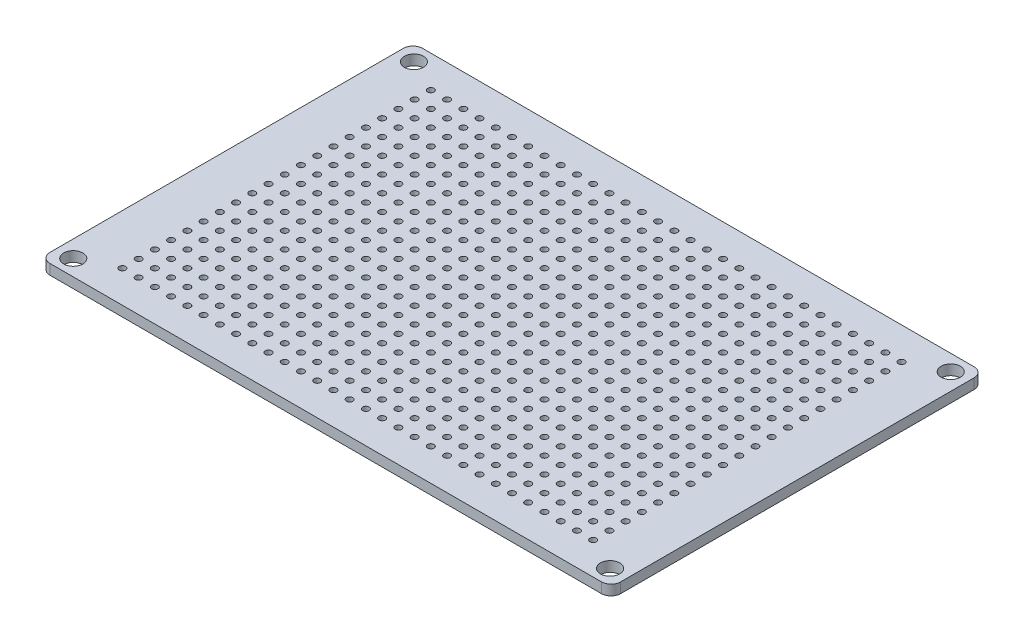
SolidWorks part; units mm, degrees
ref_plane "Front Plane" through (0, 0, 0) normal (0, 0, 1) x (1, 0, 0)
ref_plane "Top Plane" through (0, 0, 0) normal (0, 1, 0) x (1, 0, 0)
ref_plane "Right Plane" through (0, 0, 0) normal (1, 0, 0) x (0, 0, -1)
sketch "Sketch1" plane through (0, 0, 0) normal (0, 1, 0) x (1, 0, 0)
  line L0 (0, -29.15) -> (89.3, -29.15) construction
  line L1 (1.5, 0) -> (87.8, 0)
  line L2 (0, -1.5) -> (0, -56.8)
  line L3 (1.5, -58.3) -> (87.8, -58.3)
  line L4 (89.3, -1.5) -> (89.3, -56.8)
  line L5 (44.65, 0) -> (44.65, -58.3) construction
  line L6 (7.82, -5.02) -> (81.48, -5.02) construction
  line L7 (81.48, -5.02) -> (81.48, -53.28) construction
  line L9 (2.65, -2.5) -> (86.65, -2.5) construction
  line L10 (2.65, -2.5) -> (2.65, -55.8) construction
  line L11 (2.65, -55.8) -> (86.65, -55.8) construction
  line L12 (86.65, -2.5) -> (86.65, -55.8) construction
  circle A0 centre (7.82, -5.02) radius 0.5
  circle A1 centre (10.36, -5.02) radius 0.5
  circle A2 centre (12.9, -5.02) radius 0.5
  circle A3 centre (15.44, -5.02) radius 0.5
  circle A4 centre (17.98, -5.02) radius 0.5
  circle A5 centre (20.52, -5.02) radius 0.5
  circle A6 centre (23.06, -5.02) radius 0.5
  circle A7 centre (25.6, -5.02) radius 0.5
  circle A8 centre (28.14, -5.02) radius 0.5
  circle A9 centre (30.68, -5.02) radius 0.5
  circle A10 centre (33.22, -5.02) radius 0.5
  circle A11 centre (35.76, -5.02) radius 0.5
  circle A12 centre (38.3, -5.02) radius 0.5
  circle A13 centre (40.84, -5.02) radius 0.5
  circle A14 centre (43.38, -5.02) radius 0.5
  circle A15 centre (45.92, -5.02) radius 0.5
  circle A16 centre (48.46, -5.02) radius 0.5
  circle A17 centre (51, -5.02) radius 0.5
  circle A18 centre (53.54, -5.02) radius 0.5
  circle A19 centre (56.08, -5.02) radius 0.5
  circle A20 centre (58.62, -5.02) radius 0.5
  circle A21 centre (61.16, -5.02) radius 0.5
  circle A22 centre (63.7, -5.02) radius 0.5
  circle A23 centre (66.24, -5.02) radius 0.5
  circle A24 centre (68.78, -5.02) radius 0.5
  circle A25 centre (71.32, -5.02) radius 0.5
  circle A26 centre (73.86, -5.02) radius 0.5
  circle A27 centre (76.4, -5.02) radius 0.5
  circle A28 centre (78.94, -5.02) radius 0.5
  circle A29 centre (81.48, -5.02) radius 0.5
  circle A30 centre (10.36, -7.56) radius 0.5
  circle A31 centre (12.9, -7.56) radius 0.5
  circle A32 centre (15.44, -7.56) radius 0.5
  circle A33 centre (17.98, -7.56) radius 0.5
  circle A34 centre (20.52, -7.56) radius 0.5
  circle A35 centre (23.06, -7.56) radius 0.5
  circle A36 centre (25.6, -7.56) radius 0.5
  circle A37 centre (28.14, -7.56) radius 0.5
  circle A38 centre (30.68, -7.56) radius 0.5
  circle A39 centre (33.22, -7.56) radius 0.5
  circle A40 centre (35.76, -7.56) radius 0.5
  circle A41 centre (38.3, -7.56) radius 0.5
  circle A42 centre (40.84, -7.56) radius 0.5
  circle A43 centre (43.38, -7.56) radius 0.5
  circle A44 centre (45.92, -7.56) radius 0.5
  circle A45 centre (48.46, -7.56) radius 0.5
  circle A46 centre (51, -7.56) radius 0.5
  circle A47 centre (53.54, -7.56) radius 0.5
  circle A48 centre (56.08, -7.56) radius 0.5
  circle A49 centre (58.62, -7.56) radius 0.5
  circle A50 centre (61.16, -7.56) radius 0.5
  circle A51 centre (63.7, -7.56) radius 0.5
  circle A52 centre (66.24, -7.56) radius 0.5
  circle A53 centre (68.78, -7.56) radius 0.5
  circle A54 centre (71.32, -7.56) radius 0.5
  circle A55 centre (73.86, -7.56) radius 0.5
  circle A56 centre (76.4, -7.56) radius 0.5
  circle A57 centre (78.94, -7.56) radius 0.5
  circle A58 centre (81.48, -7.56) radius 0.5
  circle A59 centre (10.36, -10.1) radius 0.5
  circle A60 centre (12.9, -10.1) radius 0.5
  circle A61 centre (15.44, -10.1) radius 0.5
  circle A62 centre (17.98, -10.1) radius 0.5
  circle A63 centre (20.52, -10.1) radius 0.5
  circle A64 centre (23.06, -10.1) radius 0.5
  circle A65 centre (25.6, -10.1) radius 0.5
  circle A66 centre (28.14, -10.1) radius 0.5
  circle A67 centre (30.68, -10.1) radius 0.5
  circle A68 centre (33.22, -10.1) radius 0.5
  circle A69 centre (35.76, -10.1) radius 0.5
  circle A70 centre (38.3, -10.1) radius 0.5
  circle A71 centre (40.84, -10.1) radius 0.5
  circle A72 centre (43.38, -10.1) radius 0.5
  circle A73 centre (45.92, -10.1) radius 0.5
  circle A74 centre (48.46, -10.1) radius 0.5
  circle A75 centre (51, -10.1) radius 0.5
  circle A76 centre (53.54, -10.1) radius 0.5
  circle A77 centre (56.08, -10.1) radius 0.5
  circle A78 centre (58.62, -10.1) radius 0.5
  circle A79 centre (61.16, -10.1) radius 0.5
  circle A80 centre (63.7, -10.1) radius 0.5
  circle A81 centre (66.24, -10.1) radius 0.5
  circle A82 centre (68.78, -10.1) radius 0.5
  circle A83 centre (71.32, -10.1) radius 0.5
  circle A84 centre (73.86, -10.1) radius 0.5
  circle A85 centre (76.4, -10.1) radius 0.5
  circle A86 centre (78.94, -10.1) radius 0.5
  circle A87 centre (81.48, -10.1) radius 0.5
  circle A88 centre (10.36, -12.64) radius 0.5
  circle A89 centre (12.9, -12.64) radius 0.5
  circle A90 centre (15.44, -12.64) radius 0.5
  circle A91 centre (17.98, -12.64) radius 0.5
  circle A92 centre (20.52, -12.64) radius 0.5
  circle A93 centre (23.06, -12.64) radius 0.5
  circle A94 centre (25.6, -12.64) radius 0.5
  circle A95 centre (28.14, -12.64) radius 0.5
  circle A96 centre (30.68, -12.64) radius 0.5
  circle A97 centre (33.22, -12.64) radius 0.5
  circle A98 centre (35.76, -12.64) radius 0.5
  circle A99 centre (38.3, -12.64) radius 0.5
  circle A100 centre (40.84, -12.64) radius 0.5
  circle A101 centre (43.38, -12.64) radius 0.5
  circle A102 centre (45.92, -12.64) radius 0.5
  circle A103 centre (48.46, -12.64) radius 0.5
  circle A104 centre (51, -12.64) radius 0.5
  circle A105 centre (53.54, -12.64) radius 0.5
  circle A106 centre (56.08, -12.64) radius 0.5
  circle A107 centre (58.62, -12.64) radius 0.5
  circle A108 centre (61.16, -12.64) radius 0.5
  circle A109 centre (63.7, -12.64) radius 0.5
  circle A110 centre (66.24, -12.64) radius 0.5
  circle A111 centre (68.78, -12.64) radius 0.5
  circle A112 centre (71.32, -12.64) radius 0.5
  circle A113 centre (73.86, -12.64) radius 0.5
  circle A114 centre (76.4, -12.64) radius 0.5
  circle A115 centre (78.94, -12.64) radius 0.5
  circle A116 centre (81.48, -12.64) radius 0.5
  circle A117 centre (10.36, -15.18) radius 0.5
  circle A118 centre (12.9, -15.18) radius 0.5
  circle A119 centre (15.44, -15.18) radius 0.5
  circle A120 centre (17.98, -15.18) radius 0.5
  circle A121 centre (20.52, -15.18) radius 0.5
  circle A122 centre (23.06, -15.18) radius 0.5
  circle A123 centre (25.6, -15.18) radius 0.5
  circle A124 centre (28.14, -15.18) radius 0.5
  circle A125 centre (30.68, -15.18) radius 0.5
  circle A126 centre (33.22, -15.18) radius 0.5
  circle A127 centre (35.76, -15.18) radius 0.5
  circle A128 centre (38.3, -15.18) radius 0.5
  circle A129 centre (40.84, -15.18) radius 0.5
  circle A130 centre (43.38, -15.18) radius 0.5
  circle A131 centre (45.92, -15.18) radius 0.5
  circle A132 centre (48.46, -15.18) radius 0.5
  circle A133 centre (51, -15.18) radius 0.5
  circle A134 centre (53.54, -15.18) radius 0.5
  circle A135 centre (56.08, -15.18) radius 0.5
  circle A136 centre (58.62, -15.18) radius 0.5
  circle A137 centre (61.16, -15.18) radius 0.5
  circle A138 centre (63.7, -15.18) radius 0.5
  circle A139 centre (66.24, -15.18) radius 0.5
  circle A140 centre (68.78, -15.18) radius 0.5
  circle A141 centre (71.32, -15.18) radius 0.5
  circle A142 centre (73.86, -15.18) radius 0.5
  circle A143 centre (76.4, -15.18) radius 0.5
  circle A144 centre (78.94, -15.18) radius 0.5
  circle A145 centre (81.48, -15.18) radius 0.5
  circle A146 centre (10.36, -17.72) radius 0.5
  circle A147 centre (12.9, -17.72) radius 0.5
  circle A148 centre (15.44, -17.72) radius 0.5
  circle A149 centre (17.98, -17.72) radius 0.5
  circle A150 centre (20.52, -17.72) radius 0.5
  circle A151 centre (23.06, -17.72) radius 0.5
  circle A152 centre (25.6, -17.72) radius 0.5
  circle A153 centre (28.14, -17.72) radius 0.5
  circle A154 centre (30.68, -17.72) radius 0.5
  circle A155 centre (33.22, -17.72) radius 0.5
  circle A156 centre (35.76, -17.72) radius 0.5
  circle A157 centre (38.3, -17.72) radius 0.5
  circle A158 centre (40.84, -17.72) radius 0.5
  circle A159 centre (43.38, -17.72) radius 0.5
  circle A160 centre (45.92, -17.72) radius 0.5
  circle A161 centre (48.46, -17.72) radius 0.5
  circle A162 centre (51, -17.72) radius 0.5
  circle A163 centre (53.54, -17.72) radius 0.5
  circle A164 centre (56.08, -17.72) radius 0.5
  circle A165 centre (58.62, -17.72) radius 0.5
  circle A166 centre (61.16, -17.72) radius 0.5
  circle A167 centre (63.7, -17.72) radius 0.5
  circle A168 centre (66.24, -17.72) radius 0.5
  circle A169 centre (68.78, -17.72) radius 0.5
  circle A170 centre (71.32, -17.72) radius 0.5
  circle A171 centre (73.86, -17.72) radius 0.5
  circle A172 centre (76.4, -17.72) radius 0.5
  circle A173 centre (78.94, -17.72) radius 0.5
  circle A174 centre (81.48, -17.72) radius 0.5
  circle A175 centre (10.36, -20.26) radius 0.5
  circle A176 centre (12.9, -20.26) radius 0.5
  circle A177 centre (15.44, -20.26) radius 0.5
  circle A178 centre (17.98, -20.26) radius 0.5
  circle A179 centre (20.52, -20.26) radius 0.5
  circle A180 centre (23.06, -20.26) radius 0.5
  circle A181 centre (25.6, -20.26) radius 0.5
  circle A182 centre (28.14, -20.26) radius 0.5
  circle A183 centre (30.68, -20.26) radius 0.5
  circle A184 centre (33.22, -20.26) radius 0.5
  circle A185 centre (35.76, -20.26) radius 0.5
  circle A186 centre (38.3, -20.26) radius 0.5
  circle A187 centre (40.84, -20.26) radius 0.5
  circle A188 centre (43.38, -20.26) radius 0.5
  circle A189 centre (45.92, -20.26) radius 0.5
  circle A190 centre (48.46, -20.26) radius 0.5
  circle A191 centre (51, -20.26) radius 0.5
  circle A192 centre (53.54, -20.26) radius 0.5
  circle A193 centre (56.08, -20.26) radius 0.5
  circle A194 centre (58.62, -20.26) radius 0.5
  circle A195 centre (61.16, -20.26) radius 0.5
  circle A196 centre (63.7, -20.26) radius 0.5
  circle A197 centre (66.24, -20.26) radius 0.5
  circle A198 centre (68.78, -20.26) radius 0.5
  circle A199 centre (71.32, -20.26) radius 0.5
  circle A200 centre (73.86, -20.26) radius 0.5
  circle A201 centre (76.4, -20.26) radius 0.5
  circle A202 centre (78.94, -20.26) radius 0.5
  circle A203 centre (81.48, -20.26) radius 0.5
  circle A204 centre (10.36, -22.8) radius 0.5
  circle A205 centre (12.9, -22.8) radius 0.5
  circle A206 centre (15.44, -22.8) radius 0.5
  circle A207 centre (17.98, -22.8) radius 0.5
  circle A208 centre (20.52, -22.8) radius 0.5
  circle A209 centre (23.06, -22.8) radius 0.5
  circle A210 centre (25.6, -22.8) radius 0.5
  circle A211 centre (28.14, -22.8) radius 0.5
  circle A212 centre (30.68, -22.8) radius 0.5
  circle A213 centre (33.22, -22.8) radius 0.5
  circle A214 centre (35.76, -22.8) radius 0.5
  circle A215 centre (38.3, -22.8) radius 0.5
  circle A216 centre (40.84, -22.8) radius 0.5
  circle A217 centre (43.38, -22.8) radius 0.5
  circle A218 centre (45.92, -22.8) radius 0.5
  circle A219 centre (48.46, -22.8) radius 0.5
  circle A220 centre (51, -22.8) radius 0.5
  circle A221 centre (53.54, -22.8) radius 0.5
  circle A222 centre (56.08, -22.8) radius 0.5
  circle A223 centre (58.62, -22.8) radius 0.5
  circle A224 centre (61.16, -22.8) radius 0.5
  circle A225 centre (63.7, -22.8) radius 0.5
  circle A226 centre (66.24, -22.8) radius 0.5
  circle A227 centre (68.78, -22.8) radius 0.5
  circle A228 centre (71.32, -22.8) radius 0.5
  circle A229 centre (73.86, -22.8) radius 0.5
  circle A230 centre (76.4, -22.8) radius 0.5
  circle A231 centre (78.94, -22.8) radius 0.5
  circle A232 centre (81.48, -22.8) radius 0.5
  circle A233 centre (10.36, -25.34) radius 0.5
  circle A234 centre (12.9, -25.34) radius 0.5
  circle A235 centre (15.44, -25.34) radius 0.5
  circle A236 centre (17.98, -25.34) radius 0.5
  circle A237 centre (20.52, -25.34) radius 0.5
  circle A238 centre (23.06, -25.34) radius 0.5
  circle A239 centre (25.6, -25.34) radius 0.5
  circle A240 centre (28.14, -25.34) radius 0.5
  circle A241 centre (30.68, -25.34) radius 0.5
  circle A242 centre (33.22, -25.34) radius 0.5
  circle A243 centre (35.76, -25.34) radius 0.5
  circle A244 centre (38.3, -25.34) radius 0.5
  circle A245 centre (40.84, -25.34) radius 0.5
  circle A246 centre (43.38, -25.34) radius 0.5
  circle A247 centre (45.92, -25.34) radius 0.5
  circle A248 centre (48.46, -25.34) radius 0.5
  circle A249 centre (51, -25.34) radius 0.5
  circle A250 centre (53.54, -25.34) radius 0.5
  circle A251 centre (56.08, -25.34) radius 0.5
  circle A252 centre (58.62, -25.34) radius 0.5
  circle A253 centre (61.16, -25.34) radius 0.5
  circle A254 centre (63.7, -25.34) radius 0.5
  circle A255 centre (66.24, -25.34) radius 0.5
  circle A256 centre (68.78, -25.34) radius 0.5
  circle A257 centre (71.32, -25.34) radius 0.5
  circle A258 centre (73.86, -25.34) radius 0.5
  circle A259 centre (76.4, -25.34) radius 0.5
  circle A260 centre (78.94, -25.34) radius 0.5
  circle A261 centre (81.48, -25.34) radius 0.5
  circle A262 centre (10.36, -27.88) radius 0.5
  circle A263 centre (12.9, -27.88) radius 0.5
  circle A264 centre (15.44, -27.88) radius 0.5
  circle A265 centre (17.98, -27.88) radius 0.5
  circle A266 centre (20.52, -27.88) radius 0.5
  circle A267 centre (23.06, -27.88) radius 0.5
  circle A268 centre (25.6, -27.88) radius 0.5
  circle A269 centre (28.14, -27.88) radius 0.5
  circle A270 centre (30.68, -27.88) radius 0.5
  circle A271 centre (33.22, -27.88) radius 0.5
  circle A272 centre (35.76, -27.88) radius 0.5
  circle A273 centre (38.3, -27.88) radius 0.5
  circle A274 centre (40.84, -27.88) radius 0.5
  circle A275 centre (43.38, -27.88) radius 0.5
  circle A276 centre (45.92, -27.88) radius 0.5
  circle A277 centre (48.46, -27.88) radius 0.5
  circle A278 centre (51, -27.88) radius 0.5
  circle A279 centre (53.54, -27.88) radius 0.5
  circle A280 centre (56.08, -27.88) radius 0.5
  circle A281 centre (58.62, -27.88) radius 0.5
  circle A282 centre (61.16, -27.88) radius 0.5
  circle A283 centre (63.7, -27.88) radius 0.5
  circle A284 centre (66.24, -27.88) radius 0.5
  circle A285 centre (68.78, -27.88) radius 0.5
  circle A286 centre (71.32, -27.88) radius 0.5
  circle A287 centre (73.86, -27.88) radius 0.5
  circle A288 centre (76.4, -27.88) radius 0.5
  circle A289 centre (78.94, -27.88) radius 0.5
  circle A290 centre (81.48, -27.88) radius 0.5
  circle A291 centre (10.36, -30.42) radius 0.5
  circle A292 centre (12.9, -30.42) radius 0.5
  circle A293 centre (15.44, -30.42) radius 0.5
  circle A294 centre (17.98, -30.42) radius 0.5
  circle A295 centre (20.52, -30.42) radius 0.5
  circle A296 centre (23.06, -30.42) radius 0.5
  circle A297 centre (25.6, -30.42) radius 0.5
  circle A298 centre (28.14, -30.42) radius 0.5
  circle A299 centre (30.68, -30.42) radius 0.5
  circle A300 centre (33.22, -30.42) radius 0.5
  circle A301 centre (35.76, -30.42) radius 0.5
  circle A302 centre (38.3, -30.42) radius 0.5
  circle A303 centre (40.84, -30.42) radius 0.5
  circle A304 centre (43.38, -30.42) radius 0.5
  circle A305 centre (45.92, -30.42) radius 0.5
  circle A306 centre (48.46, -30.42) radius 0.5
  circle A307 centre (51, -30.42) radius 0.5
  circle A308 centre (53.54, -30.42) radius 0.5
  circle A309 centre (56.08, -30.42) radius 0.5
  circle A310 centre (58.62, -30.42) radius 0.5
  circle A311 centre (61.16, -30.42) radius 0.5
  circle A312 centre (63.7, -30.42) radius 0.5
  circle A313 centre (66.24, -30.42) radius 0.5
  circle A314 centre (68.78, -30.42) radius 0.5
  circle A315 centre (71.32, -30.42) radius 0.5
  circle A316 centre (73.86, -30.42) radius 0.5
  circle A317 centre (76.4, -30.42) radius 0.5
  circle A318 centre (78.94, -30.42) radius 0.5
  circle A319 centre (81.48, -30.42) radius 0.5
  circle A320 centre (10.36, -32.96) radius 0.5
  circle A321 centre (12.9, -32.96) radius 0.5
  circle A322 centre (15.44, -32.96) radius 0.5
  circle A323 centre (17.98, -32.96) radius 0.5
  circle A324 centre (20.52, -32.96) radius 0.5
  circle A325 centre (23.06, -32.96) radius 0.5
  circle A326 centre (25.6, -32.96) radius 0.5
  circle A327 centre (28.14, -32.96) radius 0.5
  circle A328 centre (30.68, -32.96) radius 0.5
  circle A329 centre (33.22, -32.96) radius 0.5
  circle A330 centre (35.76, -32.96) radius 0.5
  circle A331 centre (38.3, -32.96) radius 0.5
  circle A332 centre (40.84, -32.96) radius 0.5
  circle A333 centre (43.38, -32.96) radius 0.5
  circle A334 centre (45.92, -32.96) radius 0.5
  circle A335 centre (48.46, -32.96) radius 0.5
  circle A336 centre (51, -32.96) radius 0.5
  circle A337 centre (53.54, -32.96) radius 0.5
  circle A338 centre (56.08, -32.96) radius 0.5
  circle A339 centre (58.62, -32.96) radius 0.5
  circle A340 centre (61.16, -32.96) radius 0.5
  circle A341 centre (63.7, -32.96) radius 0.5
  circle A342 centre (66.24, -32.96) radius 0.5
  circle A343 centre (68.78, -32.96) radius 0.5
  circle A344 centre (71.32, -32.96) radius 0.5
  circle A345 centre (73.86, -32.96) radius 0.5
  circle A346 centre (76.4, -32.96) radius 0.5
  circle A347 centre (78.94, -32.96) radius 0.5
  circle A348 centre (81.48, -32.96) radius 0.5
  circle A349 centre (10.36, -35.5) radius 0.5
  circle A350 centre (12.9, -35.5) radius 0.5
  circle A351 centre (15.44, -35.5) radius 0.5
  circle A352 centre (17.98, -35.5) radius 0.5
  circle A353 centre (20.52, -35.5) radius 0.5
  circle A354 centre (23.06, -35.5) radius 0.5
  circle A355 centre (25.6, -35.5) radius 0.5
  circle A356 centre (28.14, -35.5) radius 0.5
  circle A357 centre (30.68, -35.5) radius 0.5
  circle A358 centre (33.22, -35.5) radius 0.5
  circle A359 centre (35.76, -35.5) radius 0.5
  circle A360 centre (38.3, -35.5) radius 0.5
  circle A361 centre (40.84, -35.5) radius 0.5
  circle A362 centre (43.38, -35.5) radius 0.5
  circle A363 centre (45.92, -35.5) radius 0.5
  circle A364 centre (48.46, -35.5) radius 0.5
  circle A365 centre (51, -35.5) radius 0.5
  circle A366 centre (53.54, -35.5) radius 0.5
  circle A367 centre (56.08, -35.5) radius 0.5
  circle A368 centre (58.62, -35.5) radius 0.5
  circle A369 centre (61.16, -35.5) radius 0.5
  circle A370 centre (63.7, -35.5) radius 0.5
  circle A371 centre (66.24, -35.5) radius 0.5
  circle A372 centre (68.78, -35.5) radius 0.5
  circle A373 centre (71.32, -35.5) radius 0.5
  circle A374 centre (73.86, -35.5) radius 0.5
  circle A375 centre (76.4, -35.5) radius 0.5
  circle A376 centre (78.94, -35.5) radius 0.5
  circle A377 centre (81.48, -35.5) radius 0.5
  circle A378 centre (10.36, -38.04) radius 0.5
  circle A379 centre (12.9, -38.04) radius 0.5
  circle A380 centre (15.44, -38.04) radius 0.5
  circle A381 centre (17.98, -38.04) radius 0.5
  circle A382 centre (20.52, -38.04) radius 0.5
  circle A383 centre (23.06, -38.04) radius 0.5
  circle A384 centre (25.6, -38.04) radius 0.5
  circle A385 centre (28.14, -38.04) radius 0.5
  circle A386 centre (30.68, -38.04) radius 0.5
  circle A387 centre (33.22, -38.04) radius 0.5
  circle A388 centre (35.76, -38.04) radius 0.5
  circle A389 centre (38.3, -38.04) radius 0.5
  circle A390 centre (40.84, -38.04) radius 0.5
  circle A391 centre (43.38, -38.04) radius 0.5
  circle A392 centre (45.92, -38.04) radius 0.5
  circle A393 centre (48.46, -38.04) radius 0.5
  circle A394 centre (51, -38.04) radius 0.5
  circle A395 centre (53.54, -38.04) radius 0.5
  circle A396 centre (56.08, -38.04) radius 0.5
  circle A397 centre (58.62, -38.04) radius 0.5
  circle A398 centre (61.16, -38.04) radius 0.5
  circle A399 centre (63.7, -38.04) radius 0.5
  circle A400 centre (66.24, -38.04) radius 0.5
  circle A401 centre (68.78, -38.04) radius 0.5
  circle A402 centre (71.32, -38.04) radius 0.5
  circle A403 centre (73.86, -38.04) radius 0.5
  circle A404 centre (76.4, -38.04) radius 0.5
  circle A405 centre (78.94, -38.04) radius 0.5
  circle A406 centre (81.48, -38.04) radius 0.5
  circle A407 centre (10.36, -40.58) radius 0.5
  circle A408 centre (12.9, -40.58) radius 0.5
  circle A409 centre (15.44, -40.58) radius 0.5
  circle A410 centre (17.98, -40.58) radius 0.5
  circle A411 centre (20.52, -40.58) radius 0.5
  circle A412 centre (23.06, -40.58) radius 0.5
  circle A413 centre (25.6, -40.58) radius 0.5
  circle A414 centre (28.14, -40.58) radius 0.5
  circle A415 centre (30.68, -40.58) radius 0.5
  circle A416 centre (33.22, -40.58) radius 0.5
  circle A417 centre (35.76, -40.58) radius 0.5
  circle A418 centre (38.3, -40.58) radius 0.5
  circle A419 centre (40.84, -40.58) radius 0.5
  circle A420 centre (43.38, -40.58) radius 0.5
  circle A421 centre (45.92, -40.58) radius 0.5
  circle A422 centre (48.46, -40.58) radius 0.5
  circle A423 centre (51, -40.58) radius 0.5
  circle A424 centre (53.54, -40.58) radius 0.5
  circle A425 centre (56.08, -40.58) radius 0.5
  circle A426 centre (58.62, -40.58) radius 0.5
  circle A427 centre (61.16, -40.58) radius 0.5
  circle A428 centre (63.7, -40.58) radius 0.5
  circle A429 centre (66.24, -40.58) radius 0.5
  circle A430 centre (68.78, -40.58) radius 0.5
  circle A431 centre (71.32, -40.58) radius 0.5
  circle A432 centre (73.86, -40.58) radius 0.5
  circle A433 centre (76.4, -40.58) radius 0.5
  circle A434 centre (78.94, -40.58) radius 0.5
  circle A435 centre (81.48, -40.58) radius 0.5
  circle A436 centre (10.36, -43.12) radius 0.5
  circle A437 centre (12.9, -43.12) radius 0.5
  circle A438 centre (15.44, -43.12) radius 0.5
  circle A439 centre (17.98, -43.12) radius 0.5
  circle A440 centre (20.52, -43.12) radius 0.5
  circle A441 centre (23.06, -43.12) radius 0.5
  circle A442 centre (25.6, -43.12) radius 0.5
  circle A443 centre (28.14, -43.12) radius 0.5
  circle A444 centre (30.68, -43.12) radius 0.5
  circle A445 centre (33.22, -43.12) radius 0.5
  circle A446 centre (35.76, -43.12) radius 0.5
  circle A447 centre (38.3, -43.12) radius 0.5
  circle A448 centre (40.84, -43.12) radius 0.5
  circle A449 centre (43.38, -43.12) radius 0.5
  circle A450 centre (45.92, -43.12) radius 0.5
  circle A451 centre (48.46, -43.12) radius 0.5
  circle A452 centre (51, -43.12) radius 0.5
  circle A453 centre (53.54, -43.12) radius 0.5
  circle A454 centre (56.08, -43.12) radius 0.5
  circle A455 centre (58.62, -43.12) radius 0.5
  circle A456 centre (61.16, -43.12) radius 0.5
  circle A457 centre (63.7, -43.12) radius 0.5
  circle A458 centre (66.24, -43.12) radius 0.5
  circle A459 centre (68.78, -43.12) radius 0.5
  circle A460 centre (71.32, -43.12) radius 0.5
  circle A461 centre (73.86, -43.12) radius 0.5
  circle A462 centre (76.4, -43.12) radius 0.5
  circle A463 centre (78.94, -43.12) radius 0.5
  circle A464 centre (81.48, -43.12) radius 0.5
  circle A465 centre (10.36, -45.66) radius 0.5
  circle A466 centre (12.9, -45.66) radius 0.5
  circle A467 centre (15.44, -45.66) radius 0.5
  circle A468 centre (17.98, -45.66) radius 0.5
  circle A469 centre (20.52, -45.66) radius 0.5
  circle A470 centre (23.06, -45.66) radius 0.5
  circle A471 centre (25.6, -45.66) radius 0.5
  circle A472 centre (28.14, -45.66) radius 0.5
  circle A473 centre (30.68, -45.66) radius 0.5
  circle A474 centre (33.22, -45.66) radius 0.5
  circle A475 centre (35.76, -45.66) radius 0.5
  circle A476 centre (38.3, -45.66) radius 0.5
  circle A477 centre (40.84, -45.66) radius 0.5
  circle A478 centre (43.38, -45.66) radius 0.5
  circle A479 centre (45.92, -45.66) radius 0.5
  circle A480 centre (48.46, -45.66) radius 0.5
  circle A481 centre (51, -45.66) radius 0.5
  circle A482 centre (53.54, -45.66) radius 0.5
  circle A483 centre (56.08, -45.66) radius 0.5
  circle A484 centre (58.62, -45.66) radius 0.5
  circle A485 centre (61.16, -45.66) radius 0.5
  circle A486 centre (63.7, -45.66) radius 0.5
  circle A487 centre (66.24, -45.66) radius 0.5
  circle A488 centre (68.78, -45.66) radius 0.5
  circle A489 centre (71.32, -45.66) radius 0.5
  circle A490 centre (73.86, -45.66) radius 0.5
  circle A491 centre (76.4, -45.66) radius 0.5
  circle A492 centre (78.94, -45.66) radius 0.5
  circle A493 centre (81.48, -45.66) radius 0.5
  circle A494 centre (10.36, -48.2) radius 0.5
  circle A495 centre (12.9, -48.2) radius 0.5
  circle A496 centre (15.44, -48.2) radius 0.5
  circle A497 centre (17.98, -48.2) radius 0.5
  circle A498 centre (20.52, -48.2) radius 0.5
  circle A499 centre (23.06, -48.2) radius 0.5
  circle A500 centre (25.6, -48.2) radius 0.5
  circle A501 centre (28.14, -48.2) radius 0.5
  circle A502 centre (30.68, -48.2) radius 0.5
  circle A503 centre (33.22, -48.2) radius 0.5
  circle A504 centre (35.76, -48.2) radius 0.5
  circle A505 centre (38.3, -48.2) radius 0.5
  circle A506 centre (40.84, -48.2) radius 0.5
  circle A507 centre (43.38, -48.2) radius 0.5
  circle A508 centre (45.92, -48.2) radius 0.5
  circle A509 centre (48.46, -48.2) radius 0.5
  circle A510 centre (51, -48.2) radius 0.5
  circle A511 centre (53.54, -48.2) radius 0.5
  circle A512 centre (56.08, -48.2) radius 0.5
  circle A513 centre (58.62, -48.2) radius 0.5
  circle A514 centre (61.16, -48.2) radius 0.5
  circle A515 centre (63.7, -48.2) radius 0.5
  circle A516 centre (66.24, -48.2) radius 0.5
  circle A517 centre (68.78, -48.2) radius 0.5
  circle A518 centre (71.32, -48.2) radius 0.5
  circle A519 centre (73.86, -48.2) radius 0.5
  circle A520 centre (76.4, -48.2) radius 0.5
  circle A521 centre (78.94, -48.2) radius 0.5
  circle A522 centre (81.48, -48.2) radius 0.5
  circle A523 centre (10.36, -50.74) radius 0.5
  circle A524 centre (12.9, -50.74) radius 0.5
  circle A525 centre (15.44, -50.74) radius 0.5
  circle A526 centre (17.98, -50.74) radius 0.5
  circle A527 centre (20.52, -50.74) radius 0.5
  circle A528 centre (23.06, -50.74) radius 0.5
  circle A529 centre (25.6, -50.74) radius 0.5
  circle A530 centre (28.14, -50.74) radius 0.5
  circle A531 centre (30.68, -50.74) radius 0.5
  circle A532 centre (33.22, -50.74) radius 0.5
  circle A533 centre (35.76, -50.74) radius 0.5
  circle A534 centre (38.3, -50.74) radius 0.5
  circle A535 centre (40.84, -50.74) radius 0.5
  circle A536 centre (43.38, -50.74) radius 0.5
  circle A537 centre (45.92, -50.74) radius 0.5
  circle A538 centre (48.46, -50.74) radius 0.5
  circle A539 centre (51, -50.74) radius 0.5
  circle A540 centre (53.54, -50.74) radius 0.5
  circle A541 centre (56.08, -50.74) radius 0.5
  circle A542 centre (58.62, -50.74) radius 0.5
  circle A543 centre (61.16, -50.74) radius 0.5
  circle A544 centre (63.7, -50.74) radius 0.5
  circle A545 centre (66.24, -50.74) radius 0.5
  circle A546 centre (68.78, -50.74) radius 0.5
  circle A547 centre (71.32, -50.74) radius 0.5
  circle A548 centre (73.86, -50.74) radius 0.5
  circle A549 centre (76.4, -50.74) radius 0.5
  circle A550 centre (78.94, -50.74) radius 0.5
  circle A551 centre (81.48, -50.74) radius 0.5
  circle A552 centre (10.36, -53.28) radius 0.5
  circle A553 centre (12.9, -53.28) radius 0.5
  circle A554 centre (15.44, -53.28) radius 0.5
  circle A555 centre (17.98, -53.28) radius 0.5
  circle A556 centre (20.52, -53.28) radius 0.5
  circle A557 centre (23.06, -53.28) radius 0.5
  circle A558 centre (25.6, -53.28) radius 0.5
  circle A559 centre (28.14, -53.28) radius 0.5
  circle A560 centre (30.68, -53.28) radius 0.5
  circle A561 centre (33.22, -53.28) radius 0.5
  circle A562 centre (35.76, -53.28) radius 0.5
  circle A563 centre (38.3, -53.28) radius 0.5
  circle A564 centre (40.84, -53.28) radius 0.5
  circle A565 centre (43.38, -53.28) radius 0.5
  circle A566 centre (45.92, -53.28) radius 0.5
  circle A567 centre (48.46, -53.28) radius 0.5
  circle A568 centre (51, -53.28) radius 0.5
  circle A569 centre (53.54, -53.28) radius 0.5
  circle A570 centre (56.08, -53.28) radius 0.5
  circle A571 centre (58.62, -53.28) radius 0.5
  circle A572 centre (61.16, -53.28) radius 0.5
  circle A573 centre (63.7, -53.28) radius 0.5
  circle A574 centre (66.24, -53.28) radius 0.5
  circle A575 centre (68.78, -53.28) radius 0.5
  circle A576 centre (71.32, -53.28) radius 0.5
  circle A577 centre (73.86, -53.28) radius 0.5
  circle A578 centre (76.4, -53.28) radius 0.5
  circle A579 centre (78.94, -53.28) radius 0.5
  circle A580 centre (81.48, -53.28) radius 0.5
  circle A581 centre (7.82, -7.56) radius 0.5
  circle A582 centre (7.82, -10.1) radius 0.5
  circle A583 centre (7.82, -12.64) radius 0.5
  circle A584 centre (7.82, -15.18) radius 0.5
  circle A585 centre (7.82, -17.72) radius 0.5
  circle A586 centre (7.82, -20.26) radius 0.5
  circle A587 centre (7.82, -22.8) radius 0.5
  circle A588 centre (7.82, -25.34) radius 0.5
  circle A589 centre (7.82, -27.88) radius 0.5
  circle A590 centre (7.82, -30.42) radius 0.5
  circle A591 centre (7.82, -32.96) radius 0.5
  circle A592 centre (7.82, -35.5) radius 0.5
  circle A593 centre (7.82, -38.04) radius 0.5
  circle A594 centre (7.82, -40.58) radius 0.5
  circle A595 centre (7.82, -43.12) radius 0.5
  circle A596 centre (7.82, -45.66) radius 0.5
  circle A597 centre (7.82, -48.2) radius 0.5
  circle A598 centre (7.82, -50.74) radius 0.5
  circle A599 centre (7.82, -53.28) radius 0.5
  circle A600 centre (2.65, -2.5) radius 1.5
  circle A601 centre (86.65, -2.5) radius 1.5
  circle A602 centre (86.65, -55.8) radius 1.5
  circle A603 centre (2.65, -55.8) radius 1.5
  arc A604 (87.8, 0) -> (89.3, -1.5) centre (87.8, -1.5) cw
  arc A605 (89.3, -56.8) -> (87.8, -58.3) centre (87.8, -56.8) cw
  arc A606 (0, -56.8) -> (1.5, -58.3) centre (1.5, -56.8) ccw
  arc A607 (0, -1.5) -> (1.5, 0) centre (1.5, -1.5) cw
  point P9 (81.48, -29.15)
  point P10 (44.65, -5.02)
  point P15 (2.65, -29.15)
  point P18 (44.65, -2.5)
  point P1225 (89.3, -58.3)
  point P1228 (0, -58.3)
  point P1231 (0, 0)
  dimension "D3" = 1
  dimension "D10" = 3
  dimension "D11" = 3
  dimension "D12" = 3
  dimension "D13" = 3
  dimension "D14" = 1.5
  dimension "D1" = 58.3
  dimension "D2" = 89.3
  dimension "D6" = 53.3
  dimension "D7" = 84
  dimension "D8" = 48.26
  dimension "D9" = 73.66
  dimension "D4" = 30
  dimension "D5" = 20
extrude "Boss-Extrude1" add sketch "Sketch1" along normal blind 1.6
equation "\"D11@Sketch1\"=\"D10@Sketch1\""
equation "\"D12@Sketch1\"=\"D10@Sketch1\""
equation "\"D13@Sketch1\"=\"D10@Sketch1\""
